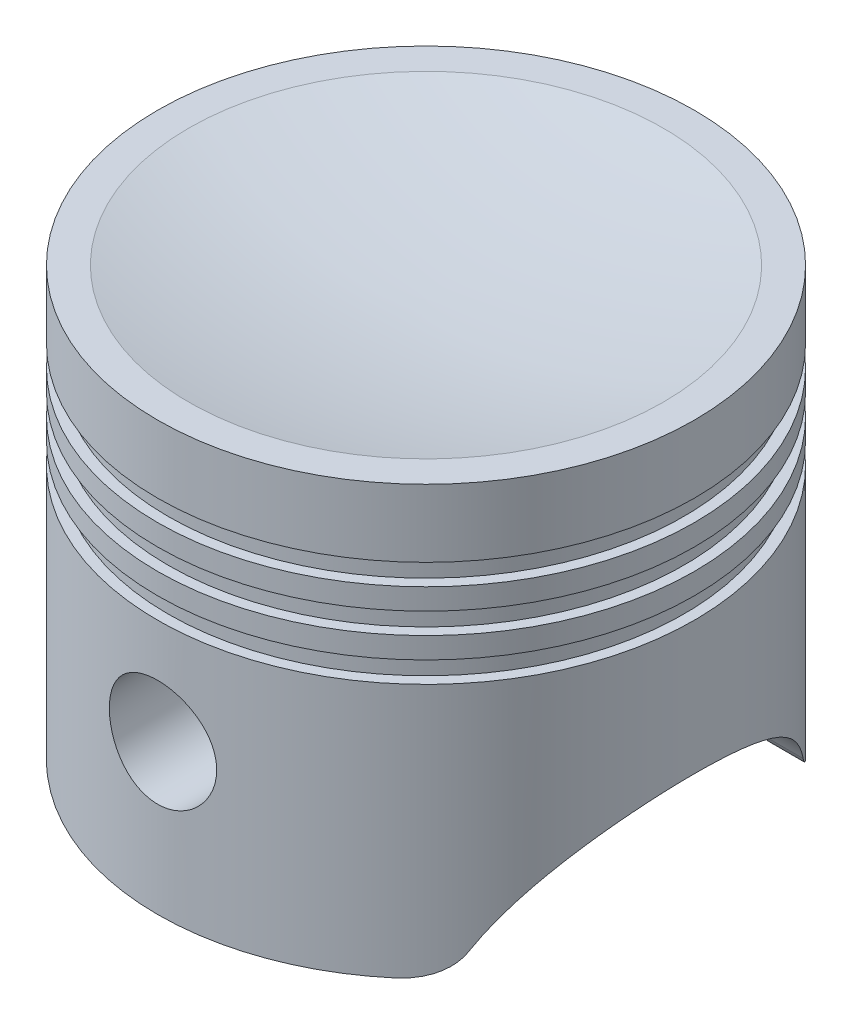
SolidWorks part; units mm, degrees
ref_plane "Front Plane" through (0, 0, 0) normal (0, 0, 1) x (1, 0, 0)
ref_plane "Top Plane" through (0, 0, 0) normal (0, 1, 0) x (1, 0, 0)
ref_plane "Right Plane" through (0, 0, 0) normal (1, 0, 0) x (0, 0, -1)
sketch "Sketch1" plane through (0, 0, 0) normal (0, 0, 1) x (1, 0, 0)
  line L0 (0, 19) -> (0, 0)
  line L1 (0, 0) -> (57.15, 0)
  line L2 (57.15, 0) -> (57.15, -75.3)
  line L3 (57.15, -75.3) -> (63.5, -75.3)
  line L4 (63.5, -75.3) -> (63.5, 26)
  line L5 (63.5, 26) -> (56.15, 26)
  arc A1 (0, 19) -> (56.15, 26) centre (-1.981, 263.592) ccw
  dimension "D7" = 244.6
  dimension "D1" = 19
  dimension "D2" = 101.3
  dimension "D3" = 6.35
  dimension "D4" = 7.35
  dimension "D5" = 63.5
  dimension "D6" = 7
revolve "Revolve1" add sketch "Sketch1" angle 360 about L0
sketch "Sketch2" plane through (0, 0, 0) normal (0, 0, 1) x (1, 0, 0)
  line L0 (63.5, -75.3) -> (63.5, 26) construction
  line L1 (61, 10) -> (63.5, 10)
  line L2 (61, 10) -> (61, 5)
  line L3 (61, 5) -> (63.5, 5)
  line L4 (63.5, 10) -> (63.5, 5)
  line L5 (0, 0) -> (0, 50.0646) construction
  dimension "D1" = 5
  dimension "D2" = 2.5
  dimension "D3" = 5
revolve "Cut-Revolve1" cut sketch "Sketch2" angle 360 about L5
pattern_linear "LPattern1" count 3 spacing 10 along (0, -1, 0) of "Cut-Revolve1"
sketch "Sketch3" plane through (0, 0, 0) normal (0, 0, 1) x (1, 0, 0)
  circle A0 centre (0, -40) radius 12.7
  dimension "D1" = 25.4
  dimension "D2" = 40
extrude "Cut-Extrude1" cut sketch "Sketch3" against normal through all both and the other way through all
sketch "Sketch4" plane through (0, 0, 0) normal (1, 0, 0) x (0, 0, -1)
  line L0 (-63.5, -75.3) -> (63.5, -75.3) construction
  arc A0 (-42, -75.3) -> (42, -75.3) centre (0, -91.4555) cw
  point P3 (0, 0)
  point P7 (0, -46.4555)
  dimension "D2" = 45
  dimension "D1" = 42
extrude "Cut-Extrude3" cut sketch "Sketch4" against normal through all and the other way through all flip side to cut
fillet "Fillet1" radius 10 4 edges at (43.1917, -75.3, -42) (-43.1917, -75.3, -42) (43.1917, -75.3, 42) (-43.1917, -75.3, 42)
sketch "Sketch5" plane through (0, 0, 0) normal (0, 0, 1) x (1, 0, 0)
  circle A0 centre (0, -40) radius 12.7 construction
  circle A1 centre (0, -40) radius 12.7
  circle A2 centre (0, -40) radius 15.2
  dimension "D1" = 2.5
extrude "Boss-Extrude1" add sketch "Sketch5" along normal up to surface (32.217 mm away) from offset 30 up to face at (2.6387, -52.4228, -63.4452)
mirror "Mirror1" about plane through (0, 0, 0) normal (0, 0, 1) of "Boss-Extrude1"
